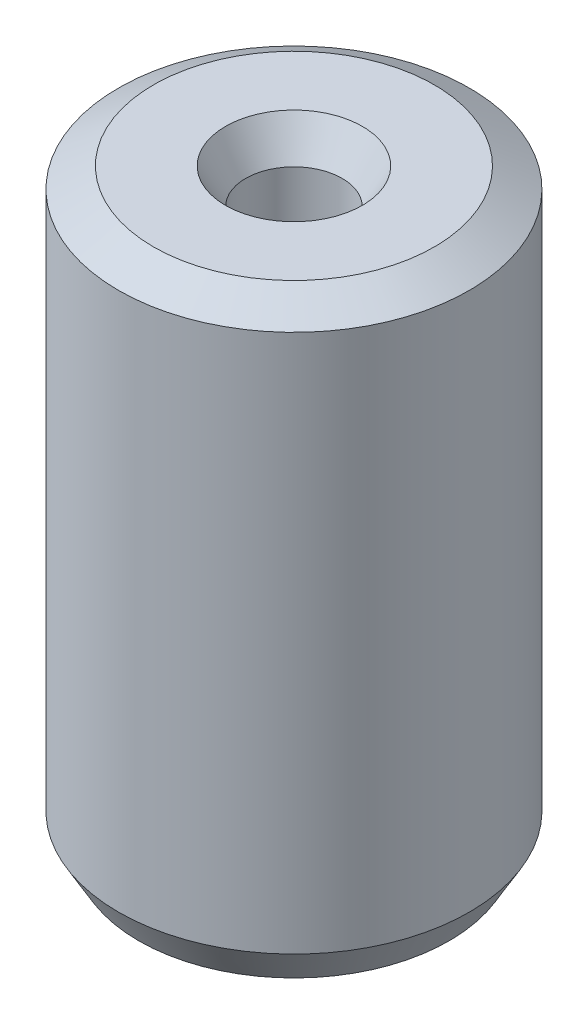
SolidWorks part; units mm, degrees
ref_plane "Front Plane" through (0, 0, 0) normal (0, 0, 1) x (1, 0, 0)
ref_plane "Top Plane" through (0, 0, 0) normal (0, 1, 0) x (1, 0, 0)
ref_plane "Right Plane" through (0, 0, 0) normal (1, 0, 0) x (0, 0, -1)
sketch "Sketch1" plane through (0, 0, 0) normal (0, 1, 0) x (1, 0, 0)
  circle A0 centre (0, 0) radius 5
  dimension "SLEEVE_OD" = 10
extrude "Boss-Extrude1" add sketch "Sketch1" along normal blind 16.9244
sketch "Sketch2" plane through (0, 0, 0) normal (0, 1, 0) x (1, 0, 0)
  circle A0 centre (0, 0) radius 1.3763
  dimension "BORE_D" = 2.7525
extrude "Cut-Extrude1" cut sketch "Sketch2" along normal through all
chamfer "Chamfer1" distance 0.5754 angle 60 4 edges at (0, 16.9244, 1.3763) (0, 0, 1.3763) (0, 0, 5) (0, 16.9244, 5) first distance on face at (0, 16.9244, 1.3763) first distance on face at (0, 0, 1.3763) first distance on face at (0, 16.9244, 5)
